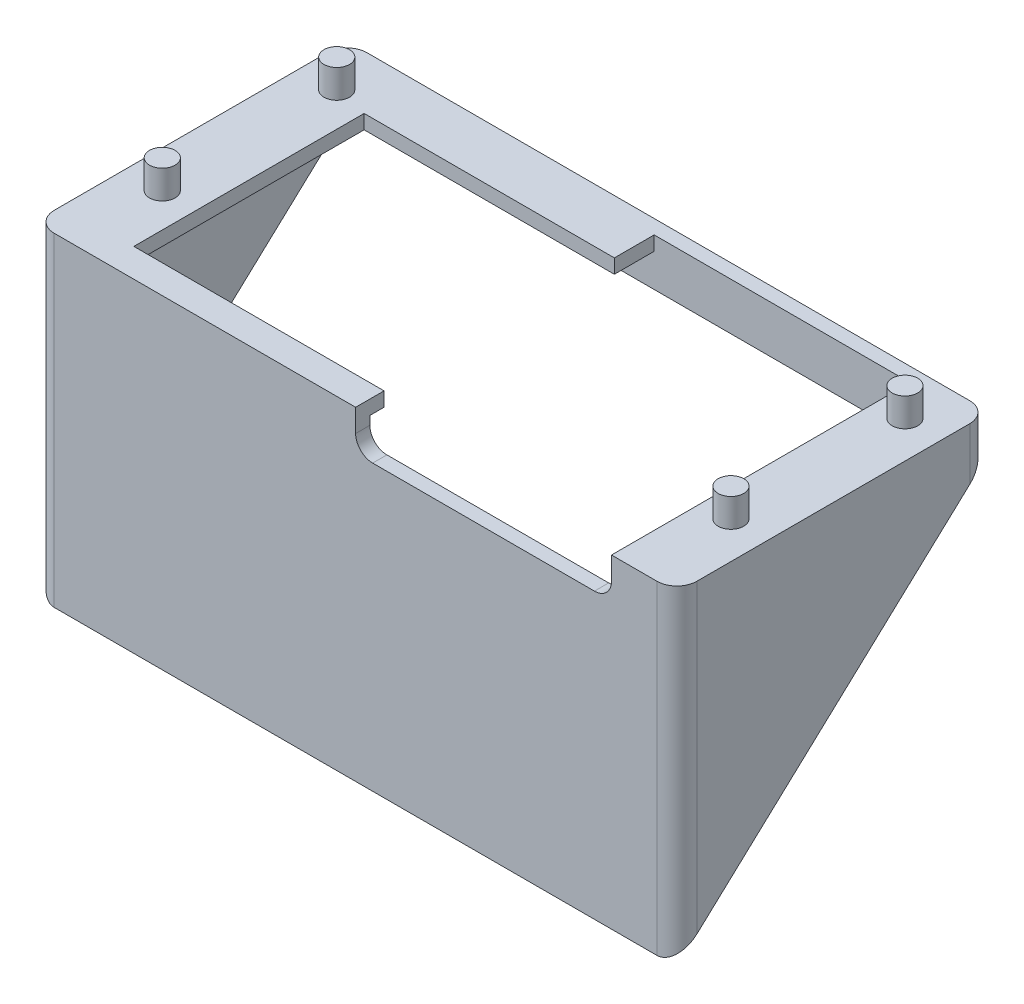
SolidWorks part; units mm, degrees
ref_plane "Front Plane" through (0, 0, 0) normal (0, 0, 1) x (1, 0, 0)
ref_plane "Top Plane" through (0, 0, 0) normal (0, 1, 0) x (1, 0, 0)
ref_plane "Right Plane" through (0, 0, 0) normal (1, 0, 0) x (0, 0, -1)
sketch "Sketch1" plane through (0, 0, 0) normal (0, 1, 0) x (1, 0, 0)
  line L1 (-52.5387, 40.0295) -> (60.4613, 40.0295)
  line L2 (-52.5387, 40.0295) -> (-52.5387, -14.9705)
  line L3 (-52.5387, -14.9705) -> (60.4613, -14.9705)
  line L4 (60.4613, 40.0295) -> (60.4613, -14.9705)
  dimension "D1" = 113
  dimension "D2" = 55
extrude "Boss-Extrude1" add sketch "Sketch1" along normal blind 6
sketch "Sketch3" plane through (60.4613, 0, 0) normal (1, 0, 0) x (0, 0, -1)
  line L0 (-14.9705, 0) -> (-14.9705, -50.9902)
  line L1 (-14.9705, -50.9902) -> (40.0295, 0)
  line L2 (40.0295, 0) -> (-14.9705, 0)
  dimension "D1" = 75
  dimension "D2" = 90
extrude "Boss-Extrude3" add sketch "Sketch3" against normal up to surface (113 mm away) up to face at (-52.5387, 3, -12.5295)
sketch "Sketch2" plane through (0, 6, 0) normal (0, 1, 0) x (1, 0, 0)
  line L0 (60.4613, -14.9705) -> (60.4613, 40.0295) construction
  line L1 (-52.5387, -14.9705) -> (60.4613, -14.9705) construction
  circle A0 centre (-46.0387, 31.7095) radius 2.25
  circle A1 centre (53.9613, 31.6295) radius 2.25
  circle A2 centre (53.9613, 1.0295) radius 2.25
  circle A3 centre (-46.0387, 1.0295) radius 2.25
  dimension "D1" = 4.5
  dimension "D2" = 4.5
  dimension "D3" = 4.5
  dimension "D4" = 4.5
  dimension "D5" = 100
  dimension "D6" = 100
  dimension "D7" = 6.5
  dimension "D8" = 6.5
  dimension "D9" = 30.68
  dimension "D10" = 30.6
  dimension "D11" = 16
  dimension "D12" = 16
extrude "Boss-Extrude2" add sketch "Sketch2" along normal blind 5
shell "Shell1" thickness 2.5 removed face at (3.9613, -25.4951, -12.5295)
sketch "Sketch4" plane through (0, 3.5, 0) normal (0, -1, 0) x (1, 0, 0)
  line L0 (-50.0387, -37.5295) -> (-50.0387, 12.4705) construction
  line L1 (-40.0387, 9.9705) -> (47.9613, 9.9705)
  line L2 (-40.0387, 9.9705) -> (-40.0387, -30.5295)
  line L3 (-40.0387, -30.5295) -> (47.9613, -30.5295)
  line L4 (47.9613, 9.9705) -> (47.9613, -30.5295)
  line L5 (57.9613, 12.4705) -> (57.9613, -37.5295) construction
  line L6 (57.9613, -37.5295) -> (-50.0387, -37.5295) construction
  line L7 (-50.0387, 12.4705) -> (57.9613, 12.4705) construction
  line L8 (57.9613, -37.5295) -> (-50.0387, -37.5295) construction
  line L9 (47.9613, -30.5295) -> (3.9613, -30.5295)
  line L10 (47.9613, -30.5295) -> (47.9613, -37.5295)
  line L11 (47.9613, -37.5295) -> (3.9613, -37.5295)
  line L12 (3.9613, -30.5295) -> (3.9613, -37.5295)
  line M6 (-50.0387, -37.5295) -> (57.9613, -37.5295)
  dimension "D1" = 10
  dimension "D2" = 10
  dimension "D3" = 7
  dimension "D4" = 2.5
extrude "Cut-Extrude1" cut sketch "Sketch4" against normal blind 10 contours L3 L12 L10 M6 | L4 L1 L2 L3 region at (3.9613, 3.5, -10.2795) region at (25.9613, 3.5, -34.0295)
fillet "Fillet2" radius 3.5 4 edges at (-52.5387, 3, -40.0295) (60.4613, 3, -40.0295) (60.4613, -22.4951, 14.9705) (-52.5387, -22.4951, 14.9705)
sketch "Sketch5" plane through (0, 0, 14.9705) normal (0, 0, 1) x (1, 0, 0)
  line L0 (-49.0387, 6) -> (56.9613, 6) construction
  line L1 (3.9613, 6) -> (48.9613, 6)
  line L2 (3.9613, 6) -> (3.9613, -1)
  line L3 (3.9613, -1) -> (48.9613, -1)
  line L4 (48.9613, 6) -> (48.9613, -1)
  line L5 (60.4613, 6) -> (60.4613, -47.7454) construction
  dimension "D1" = 11.5
  dimension "D2" = 45
  dimension "D3" = 7
extrude "Cut-Extrude2" cut sketch "Sketch5" against normal up to surface (52.5 mm away)
fillet "Fillet3" radius 3 2 edges at (48.9613, -1, 13.7205) (3.9613, -1, 13.7205)
